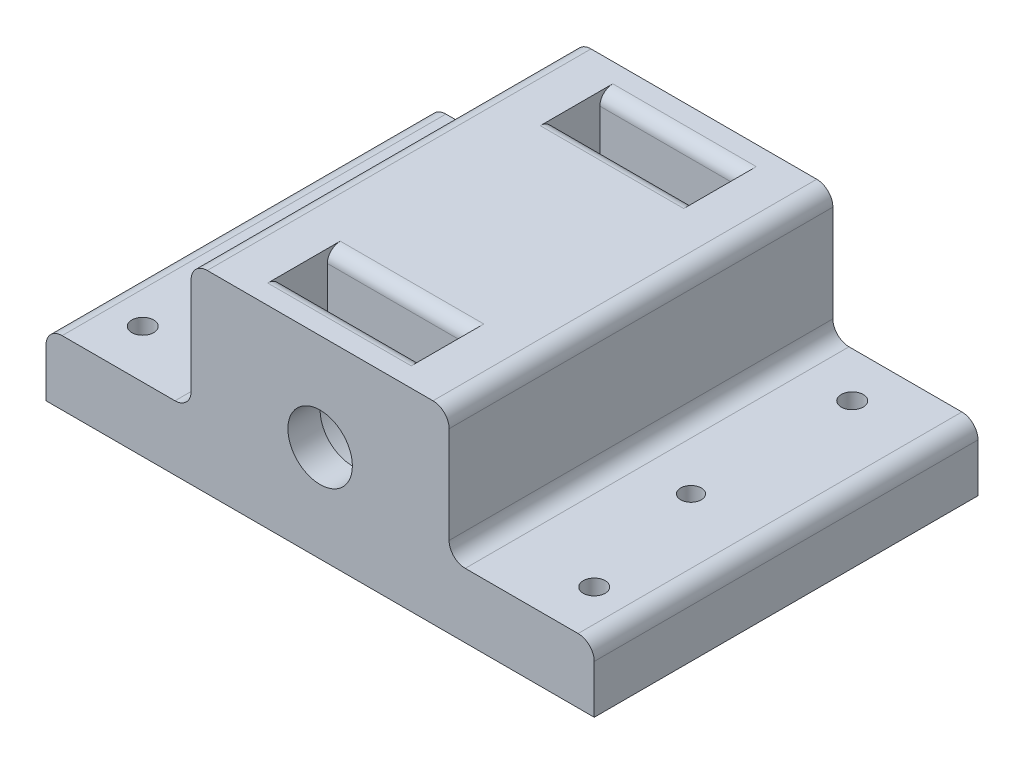
SolidWorks part; units mm, degrees
ref_plane "Front Plane" through (0, 0, 0) normal (0, 0, 1) x (1, 0, 0)
ref_plane "Top Plane" through (0, 0, 0) normal (0, 1, 0) x (1, 0, 0)
ref_plane "Right Plane" through (0, 0, 0) normal (1, 0, 0) x (0, 0, -1)
sketch "Sketch2" plane through (0, 0, 0) normal (0, 0, 1) x (1, 0, 0)
  line L0 (0, 30) -> (85, 0) construction
  line L1 (0, 0) -> (85, 0)
  line L2 (0, 0) -> (0, 30)
  line L3 (0, 30) -> (85, 30)
  line L4 (85, 0) -> (85, 30)
  line L5 (42.5, 30) -> (42.5, 15) construction
  line L6 (62.5, 30) -> (85, 30)
  line L7 (62.5, 30) -> (62.5, 10)
  line L8 (62.5, 10) -> (85, 10)
  line L9 (85, 30) -> (85, 10)
  line L10 (22.5, 10) -> (0, 10)
  line L11 (22.5, 30) -> (22.5, 10)
  circle A0 centre (42.5, 15) radius 5
  dimension "D3" = 10
  dimension "D1" = 30
  dimension "D2" = 85
  dimension "D4" = 20
  dimension "D5" = 22.5
extrude "Boss-Extrude1" add sketch "Sketch2" along normal blind 15 and the other way blind 44.5 contours L3 L11 L10 L2 L1 L4 L8 L7 A0 region at (0.9014, 5, 0)
sketch "Sketch3" plane through (0, 0, 0) normal (0, 1, 0) x (1, 0, 0)
  line L0 (0, -7.5) -> (85, -7.5) construction
  line L2 (22.5, 44.5) -> (62.5, 44.5) construction
  line L3 (42.5, 44.5) -> (42.5, -15) construction
  line L10 (0, 44.5) -> (0, -15) construction
  line L11 (85, 44.5) -> (85, -15) construction
  line L12 (22.5, -15) -> (62.5, -15) construction
  circle A0 centre (7.5, -7.5) radius 1.7
  circle A1 centre (77.5, -7.5) radius 1.7
  circle A2 centre (72.5, 12.5) radius 1.6
  circle A3 centre (12.5, 12.5) radius 1.6
  circle A4 centre (72.5, 37.5) radius 1.7
  circle A5 centre (12.5, 37.5) radius 1.7
  dimension "D1" = 3.4
  dimension "D3" = 3.2
  dimension "D4" = 20
  dimension "D6" = 7.5
  dimension "D7" = 25
  dimension "D2" = 70
  dimension "D5" = 30
extrude "Cut-Extrude1" cut sketch "Sketch3" along normal through all both and the other way through all contours A2 | A3 | A0 | A1 | A5 | A4 region at (7.5, 0, 7.5) region at (77.5, 0, 7.5) region at (72.5, 0, -12.5) region at (12.5, 0, -12.5) region at (72.5, 0, -37.5) region at (12.5, 0, -37.5)
fillet "Fillet1" radius 2.5 6 edges at (62.5, 10, -14.75) (22.5, 10, -14.75) (85, 10, -14.75) (0, 10, -14.75) (62.5, 30, -14.75) (22.5, 30, -14.75)
ref_plane "Plane1" through (0, 0, 10) normal (0, 0, 1) x (1, 0, 0)
sketch "Sketch5" plane through (0, 0, 0) normal (0, 0, 1) x (1, 0, 0)
  line L0 (42.5, 15) -> (42.5, 30) construction
  line L1 (25, 30) -> (60, 30) construction
  line L3 (31.375, 30) -> (31.375, 15)
  line L4 (31.375, 15) -> (53.625, 15) construction
  line L5 (53.625, 15) -> (53.625, 30)
  line L6 (53.625, 30) -> (31.375, 30)
  arc A0 (53.625, 15) -> (31.375, 15) centre (42.5, 15) cw
  circle A1 centre (42.5, 15) radius 5 construction
  circle A2 centre (42.5, 15) radius 5 construction
  point P5 (42.5, 3.875)
  point P12 (42.5, 15)
  dimension "D1" = 11.125
  dimension "D2" = 22.25
extrude "Cut-Extrude5" cut sketch "Sketch5" against normal blind 7.25 from surface starting at plane "Plane1"
ref_plane "Plane2" through (0, 0, -39.5) normal (0, 0, -1) x (-1, 0, 0)
extrude "Cut-Extrude6" cut sketch "Sketch5<2>" along normal blind 7.25 from surface starting at plane "Plane2"
sketch "Sketch5<2>" plane through (0, 0, 0) normal (0, 0, 1) x (1, 0, 0) same geometry as "Sketch5"
fillet "Fillet2" radius 2 4 edges at (42.5, 30, -39.5) (42.5, 30, -32.25) (42.5, 30, 2.75) (42.5, 30, 10)
equation "\"bearingthickness\"= 7mm"
equation "\"bearingOD\"= 22mm"
equation "\"D2@Sketch5\"=\"bearingOD\"+0.25mm"
equation "\"D1@Sketch5\"=\"D2@Sketch5\"/2"
equation "\"D1@Cut-Extrude5\"=\"bearingthickness\"+0.25mm"
equation "\"D1@Cut-Extrude6\"=\"bearingthickness\"+0.25mm"
